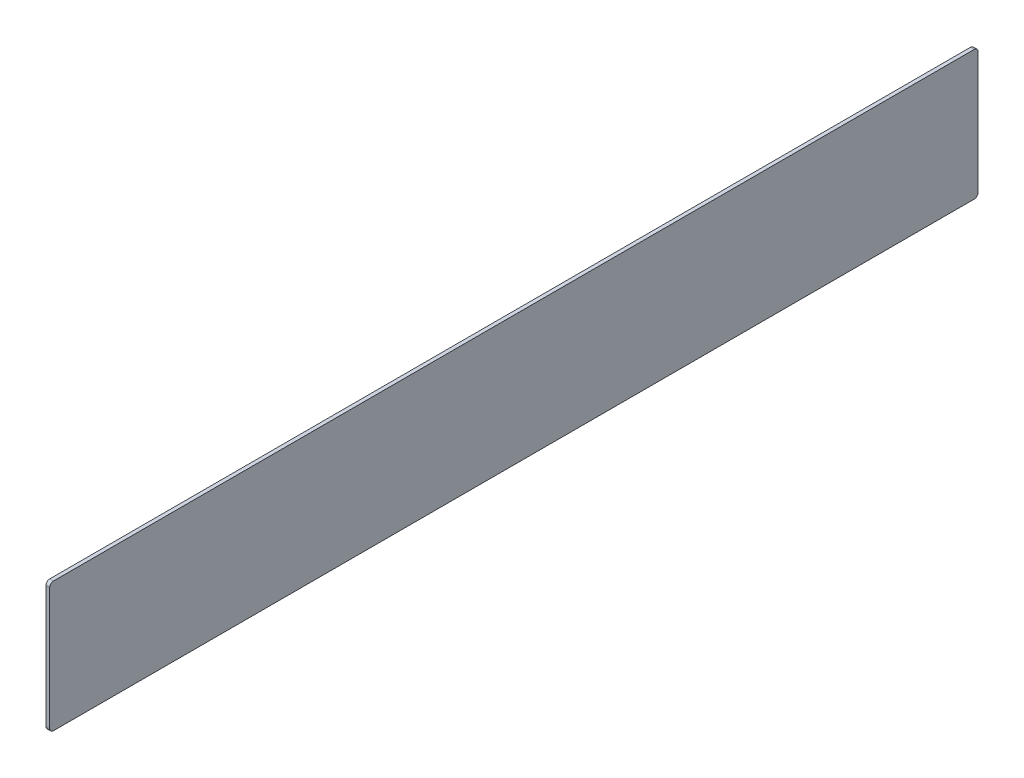
SolidWorks part; units mm, degrees
ref_plane "Front Plane" through (0, 0, 0) normal (0, 0, 1) x (1, 0, 0)
ref_plane "Top Plane" through (0, 0, 0) normal (0, 1, 0) x (1, 0, 0)
ref_plane "Right Plane" through (0, 0, 0) normal (1, 0, 0) x (0, 0, -1)
sketch "Sketch1" plane through (0, 0, 0) normal (1, 0, 0) x (0, 0, -1)
  line L1 (-269.9468, -70.4426) -> (230.0532, -70.4426)
  line L2 (-269.9468, -70.4426) -> (-269.9468, -140.2926)
  line L3 (-269.9468, -140.2926) -> (230.0532, -140.2926)
  line L4 (230.0532, -70.4426) -> (230.0532, -140.2926)
  dimension "D1" = 500
  dimension "D2" = 69.85
extrude "Boss-Extrude1" add sketch "Sketch1" along normal blind 2
fillet "Fillet1" radius 2 4 edges at (1, -140.2926, -230.0532) (1, -70.4426, -230.0532) (1, -140.2926, 269.9468) (1, -70.4426, 269.9468)
